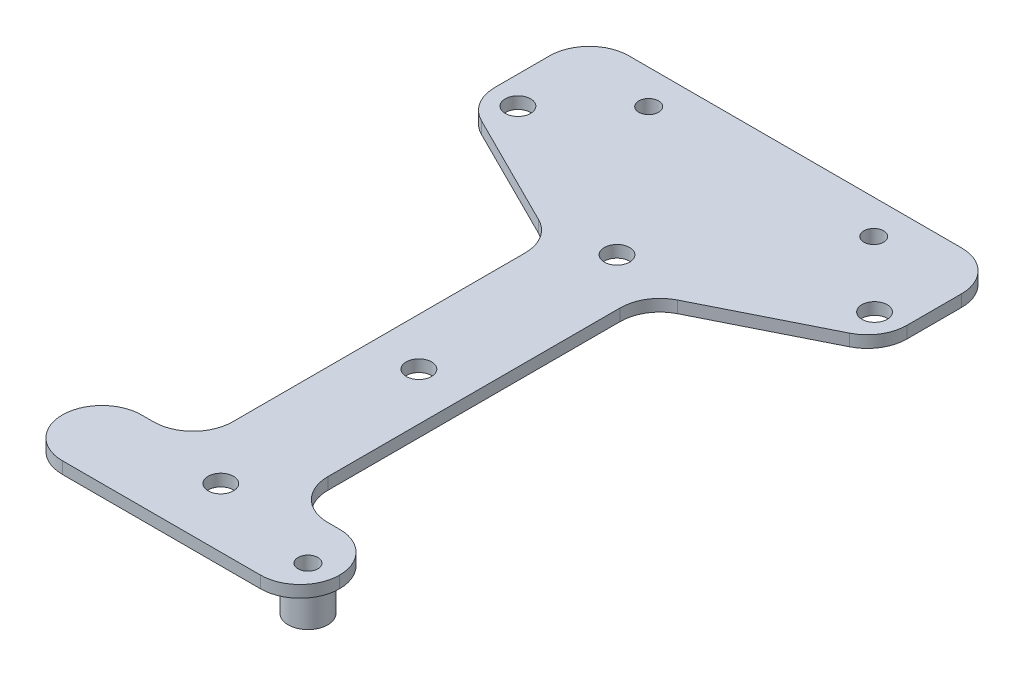
SolidWorks part; units mm, degrees
ref_plane "前视基准面" through (0, 0, 0) normal (0, 0, 1) x (1, 0, 0)
ref_plane "上视基准面" through (0, 0, 0) normal (0, 1, 0) x (1, 0, 0)
ref_plane "右视基准面" through (0, 0, 0) normal (1, 0, 0) x (0, 0, -1)
sketch "草图1" plane through (0, 0, 0) normal (0, 1, 0) x (1, 0, 0)
  line L0 (-14.2, 36.9017) -> (-14.2, -111.3942) construction
  line L1 (-40.2, 4.3) -> (11.8, 4.3)
  line L2 (-40.2, 4.3) -> (-40.2, -75.7)
  line L3 (-40.2, -75.7) -> (11.8, -75.7)
  line L4 (11.8, 4.3) -> (11.8, -75.7)
  line L5 (-40.2, 4.3) -> (11.8, -75.7) construction
  line L6 (-40.2, -75.7) -> (11.8, 4.3) construction
  line L7 (-58.9612, -30.7) -> (21.8777, -30.7) construction
  circle A0 centre (0, 0) radius 1.25
  circle A1 centre (-28.4, 0) radius 1.25
  circle A2 centre (0, -71.4) radius 1.25
  circle A3 centre (-14.2, -18.2) radius 1.6
  circle A4 centre (-14.2, -43.2) radius 1.6
  point P7 (-14.2, -35.7)
  dimension "D1" = 2.5
  dimension "D2" = 28.4
  dimension "D3" = 71.4
  dimension "D4" = 4.3
  dimension "D5" = 3.2
  dimension "D6" = 25
  dimension "D7" = 80
  dimension "D8" = 52
  dimension "D9" = 5
extrude "凸台-拉伸1" add sketch "草图1" along normal blind 1.5
cosmetic thread "装饰螺纹线1" parameters "D2"=3
cosmetic thread "装饰螺纹线2" parameters "D2"=3
cosmetic thread "装饰螺纹线3" parameters "D2"=3
sketch "草图3" plane through (0, 1.5, 0) normal (0, 1, 0) x (1, 0, 0)
  circle A0 centre (-28.4, 0) radius 1.25
  circle A1 centre (-28.4, 0) radius 2.5
  circle A2 centre (0, 0) radius 1.25
  circle A3 centre (0, 0) radius 2.5
  circle A4 centre (0, -71.4) radius 1.25
  circle A5 centre (0, -71.4) radius 2.5
  dimension "D1" = 2.5
  dimension "D2" = 5
extrude "凸台-拉伸2" add sketch "草图3" against normal blind 5.5
sketch "草图4" plane through (0, 0, 0) normal (0, -1, 0) x (1, 0, 0)
  line L0 (-14.2, -4.3) -> (-14.2, 95.7248) construction
  line L1 (11.8, -4.3) -> (-40.2, -4.3) construction
  circle A0 centre (-14.2, 68.2) radius 1.6
  circle A1 centre (8.3, 8.2) radius 1.6
  circle A2 centre (-36.7, 8.2) radius 1.6
  circle A5 centre (-14.2, 43.2) radius 1.6 construction
  dimension "D1" = 45
  dimension "D2" = 25
  dimension "D3" = 3.2
  dimension "D4" = 60
extrude "切除-拉伸2" cut sketch "草图4" against normal blind 10
sketch "草图5" plane through (0, 0, 0) normal (0, -1, 0) x (1, 0, 0)
  line L0 (-14.2, 75.7) -> (-14.2, -20.5701) construction
  line L1 (-40.2, 75.7) -> (11.8, 75.7) construction
  line L2 (-40.2, 10.7) -> (-20.2, 20.7)
  line L3 (-40.2, -4.3) -> (-40.2, 75.7) construction
  line L4 (-20.2, 20.7) -> (-20.2, 65.7)
  line L5 (-20.2, 65.7) -> (-31.7, 65.7)
  line L6 (-31.7, 65.7) -> (-31.7, 75.7)
  line L7 (-31.7, 75.7) -> (-40.2, 75.7)
  line L8 (-40.2, 75.7) -> (-40.2, 10.7)
  line L9 (11.8, 10.7) -> (-8.2, 20.7)
  line L10 (11.8, 75.7) -> (11.8, 10.7)
  line L11 (3.3, 75.7) -> (11.8, 75.7)
  line L12 (3.3, 65.7) -> (3.3, 75.7)
  line L13 (-8.2, 65.7) -> (3.3, 65.7)
  line L14 (-8.2, 20.7) -> (-8.2, 65.7)
  line L15 (11.8, -4.3) -> (-40.2, -4.3) construction
  dimension "D1" = 12
  dimension "D2" = 15
  dimension "D3" = 25
  dimension "D4" = 10
  dimension "D5" = 35
extrude "切除-拉伸3" cut sketch "草图5" against normal blind 10
fillet "圆角1" radius 5 12 edges at (-20.2, 0.75, 65.7) (-20.2, 0.75, 20.7) (-40.2, 0.75, 10.7) (-40.2, 0.75, -4.3) (11.8, 0.75, -4.3) (11.8, 0.75, 10.7) (-8.2, 0.75, 20.7) (-8.2, 0.75, 65.7) (3.3, 0.75, 65.7) (3.3, 0.75, 75.7) (-31.7, 0.75, 65.7) (-31.7, 0.75, 75.7)
